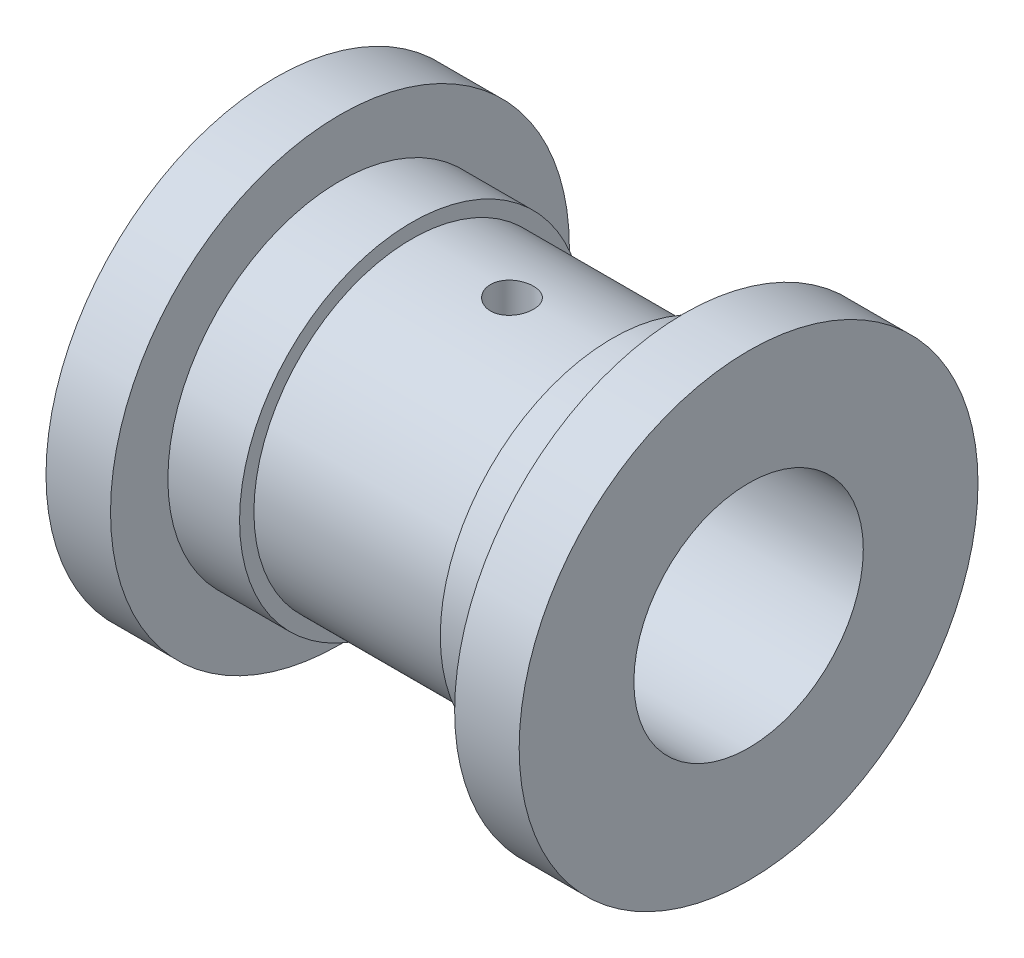
SolidWorks part; units mm, degrees
ref_plane "Front Plane" through (0, 0, 0) normal (0, 0, 1) x (1, 0, 0)
ref_plane "Top Plane" through (0, 0, 0) normal (0, 1, 0) x (1, 0, 0)
ref_plane "Right Plane" through (0, 0, 0) normal (1, 0, 0) x (0, 0, -1)
sketch "Sketch1" plane through (0, 0, 0) normal (0, 1, 0) x (1, 0, 0)
  line L0 (14, -24) -> (24, -24)
  line L1 (-14, 22) -> (14, 22)
  line L3 (-14, -22) -> (14, -22)
  line L5 (-14, 24) -> (-24, 24)
  line L6 (-14, -24) -> (-24, -24)
  line L7 (24, 32) -> (33, 32)
  line L9 (24, -32) -> (33, -32)
  line L10 (33, 32) -> (33, -32)
  line L11 (-14, -24) -> (-14, 24)
  line L12 (-24, -32) -> (-24, 32)
  line L13 (14, -24) -> (14, 24)
  line L14 (24, -32) -> (24, 32)
  line L15 (14, 24) -> (24, 24)
  line L16 (0, 0) -> (0, -22) construction
  line L17 (0, 0) -> (14, 24) construction
  line L18 (14, -24) -> (0, 0) construction
  line L19 (0, -22) -> (0, 22)
  line L20 (-24, -32) -> (-33, -32)
  line L21 (-33, 32) -> (-33, -32)
  line L22 (0, 0) -> (14.8449, -22) construction
  line L23 (0, 0) -> (33, -32) construction
  line L24 (0, 0) -> (33, 32) construction
  line L25 (0, 0) -> (14.8449, 22) construction
  line L26 (-24, 32) -> (-33, 32)
  line L27 (-33, 0) -> (33, 0)
  circle A2 centre (0, 0) radius 3
  circle A3 centre (0, 0) radius 4
  point P31 (0, 0)
  dimension "D1" = 9
  dimension "D2" = 48
  dimension "D3" = 44
  dimension "D4" = 48
  dimension "D5" = 64
  dimension "D6" = 28
revolve "Revolve8" add sketch "Sketch1" angle 360 about L27 region at (19, 0, -12) region at (28.5, 0, -16) region at (7.2255, 0, -11.3957) region at (2.2433, 0, -2.2433) region at (-19, 0, -12) region at (-7.2255, 0, -11.3957) region at (-2.2433, 0, -2.2433) region at (1.2732, 0, -1.2732) region at (-28.5, 0, -16) region at (-1.2732, 0, -1.2732)
extrude "Cut-Extrude1" cut sketch "Sketch1<4>" against normal through all both and the other way through all contours L19 A2 L27 | L27 A2 L19 | L19 A2 L27 | L27 A2 L19 region at (-1.2732, 0, 1.2732) region at (1.2732, 0, 1.2732) region at (1.2732, 0, -1.2732) region at (-1.2732, 0, -1.2732)
sketch "Sketch1<4>" plane through (0, 0, 0) normal (0, 1, 0) x (1, 0, 0) same geometry as "Sketch1"
sketch "Sketch2" plane through (33, 0, 0) normal (1, 0, 0) x (0, 0, -1)
  circle A0 centre (0, 0) radius 16
  dimension "D1" = 32
extrude "Cut-Extrude2" cut sketch "Sketch2" against normal through all both and the other way through all
